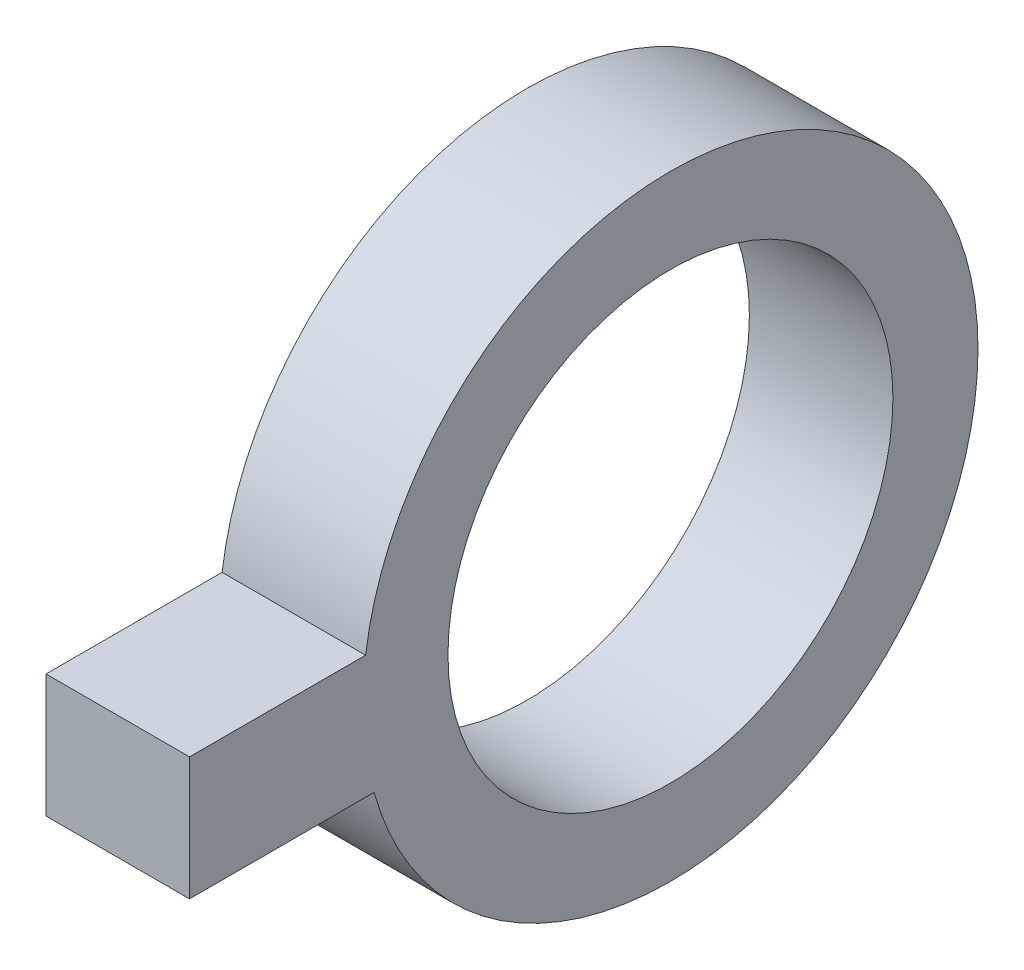
SolidWorks part; units mm, degrees
ref_plane "Front Plane" through (0, 0, 0) normal (0, 0, 1) x (1, 0, 0)
ref_plane "Top Plane" through (0, 0, 0) normal (0, 1, 0) x (1, 0, 0)
ref_plane "Right Plane" through (0, 0, 0) normal (1, 0, 0) x (0, 0, -1)
sketch "Sketch1" plane through (0, 0, 0) normal (0, 1, 0) x (1, 0, 0)
  line L0 (0, 40) -> (0, -30) construction
  line L1 (-11.547, 40) -> (-40.4145, -10)
  line L2 (-28.8675, -30) -> (28.8675, -30)
  line L3 (40.4145, -10) -> (11.547, 40)
  line L4 (11.547, 40) -> (-11.547, 40)
  line L5 (-40.4145, -10) -> (-28.8675, -30)
  line L6 (28.8675, -30) -> (40.4145, -10)
  circle A0 centre (0, 0) radius 30 construction
  circle A1 centre (0, 0) radius 40 construction
  dimension "D2" = 40
  dimension "D1" = 30
  dimension "D3" = 50
extrude "Boss-Extrude1" add sketch "Sketch1" along normal blind 6 contours L4 L1 L5 L2 L6 L3
sketch "Sketch2" plane through (0, 6, 0) normal (0, 1, 0) x (1, 0, 0)
  line L0 (0, 40) -> (0, -30) construction
  line L1 (11.547, 40) -> (-11.547, 40) construction
  line L2 (-28.8675, -30) -> (28.8675, -30) construction
  circle A0 centre (0, 0) radius 5
  dimension "D1" = 10
extrude "Cut-Extrude1" cut sketch "Sketch2" against normal blind 107
sketch "Sketch3" plane through (0, 0, 0) normal (1, 0, 0) x (0, 0, -1)
  line L0 (-34.0107, 3.4198) -> (36.0547, 3.8848) construction
  circle A0 centre (54.4549, 4.0069) radius 15
  dimension "D1" = 30
extrude "Boss-Extrude2" add sketch "Sketch3" along normal blind 3.5 and the other way blind 3.5
sketch "Sketch4" plane through (3.5, 0, 0) normal (1, 0, 0) x (0, 0, -1)
  circle A0 centre (54.4549, 4.0069) radius 10.85
  dimension "D1" = 21.7
extrude "Cut-Extrude2" cut sketch "Sketch4" against normal blind 19.5
pattern_circular "CirPattern1" count 3 over 360 about axis through (0, -101, 0) along (0, 1, 0) of bodies 104
sketch "Sketch6" plane through (0, 6, 0) normal (0, 1, 0) x (1, 0, 0)
  circle A0 centre (0, 0) radius 5
extrude "Boss-Extrude3" add sketch "Sketch6" against normal blind 34
sketch "Sketch8" plane through (0, -28, 0) normal (0, -1, 0) x (-1, 0, 0)
  line L0 (0, 0) -> (0, 50000) construction
  line L1 (0, 10) -> (0, -10)
  arc A0 (0, -10) -> (0, 10) centre (0, 0) ccw
  dimension "D1" = 20
revolve "Revolve1" add sketch "Sketch8" angle 360 about L0
sketch "Sketch12" plane through (3.5, 0, 0) normal (1, 0, 0) x (0, 0, -1)
  line L0 (40, 0) -> (40, 6) construction
  line L1 (31, 31.2162) -> (-50.7812, 31.2162)
  line L2 (31, 31.2162) -> (31, -51.2761)
  line L3 (31, -51.2761) -> (-50.7812, -51.2761)
  line L4 (-50.7812, 31.2162) -> (-50.7812, -51.2761)
  point P6 (40, 3)
  dimension "D1" = 9
extrude "Cut-Extrude5" cut sketch "Sketch12" against normal through all both and the other way through all
sketch "Sketch13" plane through (0, 0, -40) normal (0, 0, -1) x (-1, 0, 0)
  line L1 (3.5, 6) -> (21.3737, 6)
  line L2 (3.5, 6) -> (3.5, -7.3881)
  line L3 (3.5, -7.3881) -> (21.3737, -7.3881)
  line L4 (21.3737, 6) -> (21.3737, -7.3881)
  line L5 (-3.5, 6) -> (-19.3994, 6)
  line L6 (-3.5, 6) -> (-3.5, -5.8001)
  line L7 (-3.5, -5.8001) -> (-19.3994, -5.8001)
  line L8 (-19.3994, 6) -> (-19.3994, -5.8001)
extrude "Cut-Extrude6" cut sketch "Sketch13" against normal through all both
